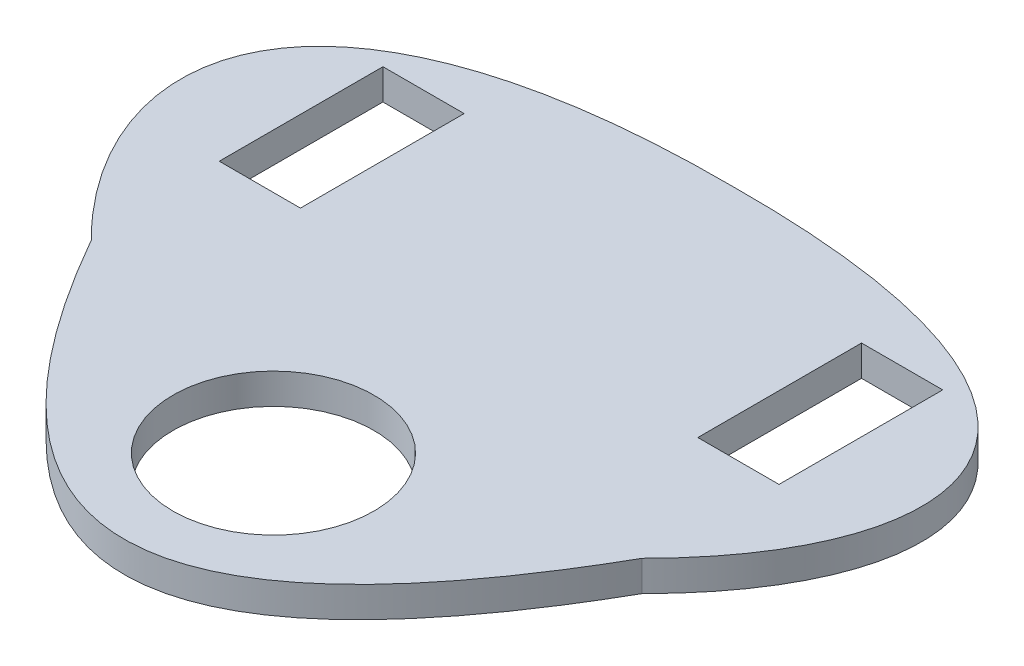
SolidWorks part; units mm, degrees
ref_plane "Front Plane" through (0, 0, 0) normal (0, 0, 1) x (1, 0, 0)
ref_plane "Top Plane" through (0, 0, 0) normal (0, 1, 0) x (1, 0, 0)
ref_plane "Right Plane" through (0, 0, 0) normal (1, 0, 0) x (0, 0, -1)
sketch "Sketch1" plane through (0, 0, 0) normal (0, 1, 0) x (1, 0, 0)
  line L0 (-50.7636, 0) -> (39.2364, 0) construction
  line L1 (39.2364, -39.6176) -> (-50.7636, -39.6176) construction
  line L2 (-50.7636, 0) -> (-50.7636, -39.6176) construction
  line L3 (39.2364, 0) -> (39.2364, -39.6176) construction
  line L4 (-5.7636, -39.6176) -> (-5.7636, 60) construction
  line L5 (-76.4362, 60) -> (59.5851, 60) construction
  line L6 (-5.7636, 35) -> (-44.855, 35) construction
  line L7 (-7.3923, 60.0049) -> (-7.3923, 0) construction
  line L8 (-44.855, 60) -> (-44.855, 35) construction
  line L9 (-27.6876, 0) -> (-27.6876, -39.6176) construction
  line L10 (39.9603, 21.6276) -> (26.6955, 21.6276)
  line L11 (-51.4874, 48.3724) -> (-38.2226, 48.3724)
  line L12 (-51.4874, 48.3724) -> (-51.4874, 21.6276)
  line L13 (-51.4874, 21.6276) -> (-38.2226, 21.6276)
  line L14 (-38.2226, 48.3724) -> (-38.2226, 21.6276)
  line L15 (-51.4874, 48.3724) -> (-38.2226, 21.6276) construction
  line L16 (-51.4874, 21.6276) -> (-38.2226, 48.3724) construction
  line L17 (26.6955, 48.3724) -> (26.6955, 21.6276)
  line L18 (39.9603, 48.3724) -> (26.6955, 48.3724)
  line L19 (39.9603, 48.3724) -> (39.9603, 21.6276)
  line L20 (39.9603, 21.6276) -> (26.6955, 48.3724) construction
  line L21 (-50.7636, -15.2373) -> (39.2364, -15.2373) construction
  line L22 (39.9603, 48.3724) -> (26.6955, 21.6276) construction
  circle A0 centre (-5.7636, -15.2373) radius 16.4173
  spline S0 degree 2 poles (-50.7636, 0) (-5.7636, -79.2352) (39.2364, 0) knots 0 0 0 1 1 1
  spline S1 degree 3 poles (-50.7636, 0) (-76.9258, 26.0498) (-74.9674, 60.482) (-5.7636, 60) knots 0 0 0 0 1 1 1 1
  spline S2 degree 3 poles (39.2364, 0) (65.3987, 26.0498) (63.4403, 60.482) (-5.7636, 60) knots 0 0 0 0 1 1 1 1
  point P26 (33.3279, 35)
extrude "Boss-Extrude1" add sketch "Sketch1" along normal blind 5
